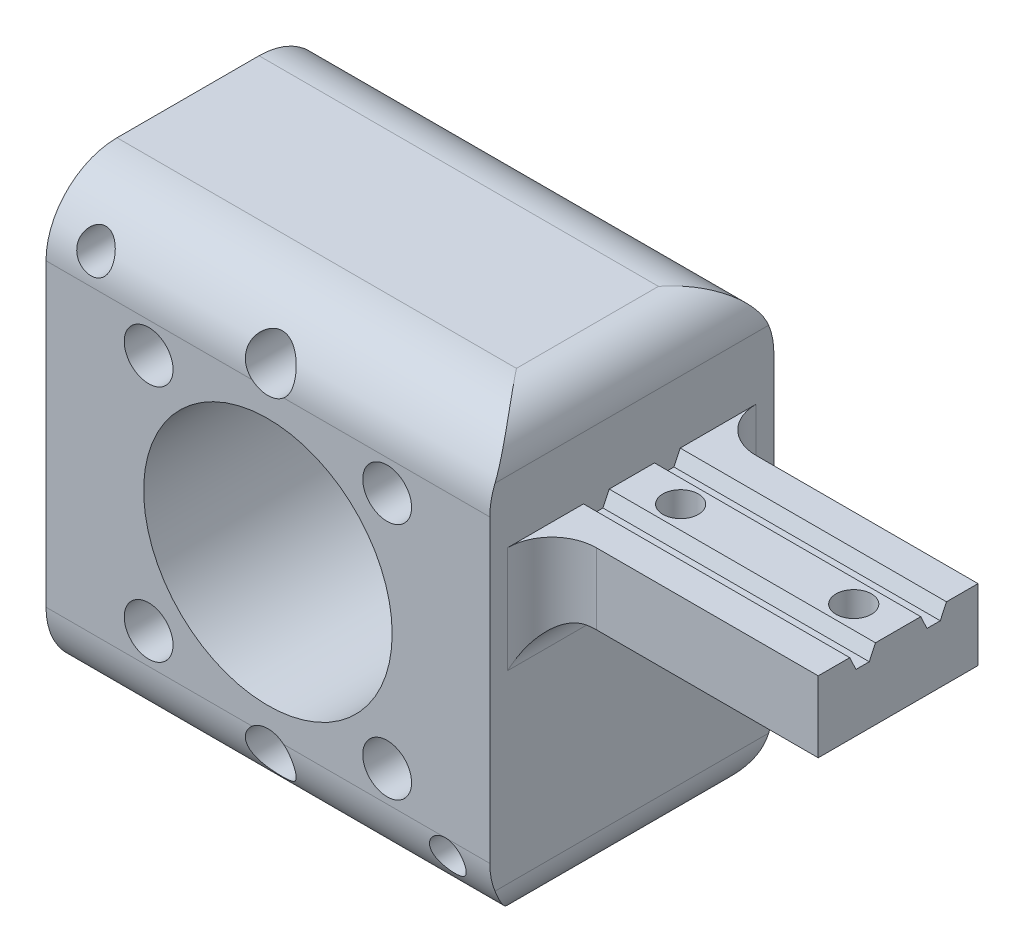
SolidWorks part; units mm, degrees
material "Alloy Steel"
ref_plane "Front Plane" through (0, 0, 0) normal (0, 0, 1) x (1, 0, 0)
ref_plane "Top Plane" through (0, 0, 0) normal (0, 1, 0) x (1, 0, 0)
ref_plane "Right Plane" through (0, 0, 0) normal (1, 0, 0) x (0, 0, -1)
sketch "Sketch1" plane through (0, 0, 0) normal (0, 0, 1) x (1, 0, 0)
  line L0 (-25, -24.9) -> (-25, 24.9)
  line L1 (-25, -24.9) -> (25, -24.9)
  line L2 (-25, 24.9) -> (25, 24.9)
  line L3 (25, 24.9) -> (25, -24.9)
  line L4 (-25, 24.9) -> (25, -24.9) construction
  circle A0 centre (0, 0) radius 14
  point P0 (0, 0)
  dimension "D1" = 28
  dimension "D2" = 49.8
  dimension "D4" = 50
extrude "Boss-Extrude1" add sketch "Sketch1" along normal blind 32
sketch "Sketch3" plane through (0, 0, 32) normal (0, 0, 1) x (1, 0, 0)
  circle A0 centre (0, 0) radius 24
  dimension "D1" = 48
extrude "Cut-Extrude1" [suppressed] cut sketch "Sketch3" against normal blind 10
sketch "Sketch5" plane through (0, 0, 32) normal (0, 0, 1) x (1, 0, 0)
  line L0 (25, 24.9) -> (-25, 24.9) construction
  line L1 (-25, 24.9) -> (-25, -24.9) construction
  line L2 (25, -24.9) -> (25, 24.9) construction
  line L3 (-25, -24.9) -> (25, -24.9) construction
  circle A0 centre (20, -18.9) radius 2
  circle A1 centre (-20, 19.9) radius 2
  dimension "D1" = 4
  dimension "D2" = 4
  dimension "D3" = 5
  dimension "D4" = 5
  dimension "D5" = 5
  dimension "D6" = 6
extrude "Cut-Extrude2" cut sketch "Sketch5" against normal through all
ref_plane "Plane3" through (0, 0, 25) normal (0, 0, -1) x (-1, 0, 0)
sketch "Sketch12" plane through (0, 0, 25) normal (0, 0, -1) x (-1, 0, 0)
  line L0 (-25, 24.9) -> (25, 24.9) construction
  line L1 (-25, 12.9) -> (-55, 12.9)
  line L2 (-25, 12.9) -> (-25, 4.9)
  line L3 (-25, 4.9) -> (-55, 4.9)
  line L4 (-55, 12.9) -> (-55, 4.9)
  dimension "D1" = 8
  dimension "D2" = 30
  dimension "D3" = 12
extrude "Boss-Extrude3" add sketch "Sketch12" along normal blind 18
sketch "Sketch13" plane through (55, 0, 0) normal (1, 0, 0) x (0, 0, -1)
  line L0 (-7, 4.9) -> (-7, 12.9) construction
  line L1 (-25, 12.9) -> (-7, 12.9)
  line L2 (-25, 12.9) -> (-25, 9.5863)
  line L3 (-20.75, 11.4) -> (-19.25, 11.4)
  line L4 (-7, 12.9) -> (-7, 11.4)
  line L5 (-7, 12.9) -> (-7, 4.9) construction
  line L6 (-25, 12.9) -> (-7, 12.9)
  line L7 (-25, 12.9) -> (-25, 10.6)
  line L8 (-25, 10.6) -> (-7, 10.6)
  line L9 (-7, 12.9) -> (-7, 10.6)
  line L10 (-10.5505, 12.9) -> (-11.25, 11.4)
  line L11 (-11.25, 11.4) -> (-12.75, 11.4)
  line L12 (-12.75, 11.4) -> (-13.4495, 12.9)
  line L13 (-7, 12.9) -> (-25, 12.9) construction
  line L14 (-19.2255, 9.5863) -> (-19.2255, 10.6) construction
  line L15 (-18.5505, 12.9) -> (-19.25, 11.4)
  line L16 (-20.75, 11.4) -> (-21.4495, 12.9)
  line L17 (-12.75, 11.4) -> (-7, 11.4)
  line L18 (-18.5505, 12.9) -> (-21.4495, 12.9)
  line L20 (-19.25, 11.4) -> (-20.75, 11.4)
  point P19 (-20, 11.4)
  point P25 (-12, 11.4)
  point P26 (-16, 12.9)
  dimension "D1" = 1.5
  dimension "D2" = 2.3
  dimension "D3" = 50
  dimension "D4" = 8
  dimension "D5" = 50
  dimension "D6" = 1.5
  dimension "D7" = 1.5
  dimension "D8" = 4
extrude "Cut-Extrude3" cut sketch "Sketch13" against normal up to surface (30 mm away) contours L16 L3 L15 L6 | L12 L11 L10 L6 region at (55, 12.2295, 20) region at (55, 12.2295, 12) up to face at (25, 0, 16)
fillet "Fillet5" radius 5 1 edges at (25, 8.9, 25)
fillet "Fillet6" radius 5 1 edges at (25, 8.9, 7)
fillet "Fillet8" radius 4 1 edges at (25, 4.9, 16)
sketch "Sketch14" plane through (0, 12.9, 0) normal (0, 1, 0) x (1, 0, 0)
  line L0 (30.5, -16) -> (50, -16) construction
  line L1 (50, -16) -> (55, -16) construction
  line L2 (55, -13.4495) -> (55, -18.5505) construction
  circle A0 centre (50, -16) radius 2
  circle A1 centre (30.5, -16) radius 2
  dimension "D1" = 4
  dimension "D2" = 4
  dimension "D3" = 19.5
  dimension "D4" = 5
extrude "Cut-Extrude4" cut sketch "Sketch14" against normal blind 10
sketch "Sketch16" plane through (0, 0, 32) normal (0, 0, 1) x (1, 0, 0)
  line L0 (-20, 14.1076) -> (-20, -14.1076) construction
  line L1 (20, 14.1076) -> (20, -14.1076) construction
  arc A0 (-20, -14.1076) -> (20, -14.1076) centre (0, 0) ccw construction
  arc A1 (20, 14.1076) -> (-20, 14.1076) centre (0, 0) ccw construction
  circle A2 centre (0, 19) radius 2.75
  circle A4 centre (13.435, 13.435) radius 2.75
  circle A6 centre (13.435, -13.435) radius 2.75
  circle A7 centre (0, -19) radius 2.75
  circle A8 centre (-13.435, -13.435) radius 2.75
  circle A10 centre (-13.435, 13.435) radius 2.75
  circle A11 centre (0, 0) radius 19 construction
  circle A12 centre (19, 0) radius 2.75 [skipped]
  circle A13 centre (-19, 0) radius 2.75 [skipped]
  point P24 (0, 0)
  dimension "D1" = 48.95
  dimension "D3" = 5.5
  dimension "D4" = 8
  dimension "D2" = 40
  dimension "D5" = 19
extrude "Cut-Extrude5" cut sketch "Sketch16" against normal through all
fillet "Fillet10" radius 8 4 edges at (0, -24.9, 0) (0, 24.9, 0) (0, -24.9, 32) (0, 24.9, 32)
fillet "Fillet11" radius 5 2 edges at (25, -24.9, 16) (25, 24.9, 16) tangent propagation no
